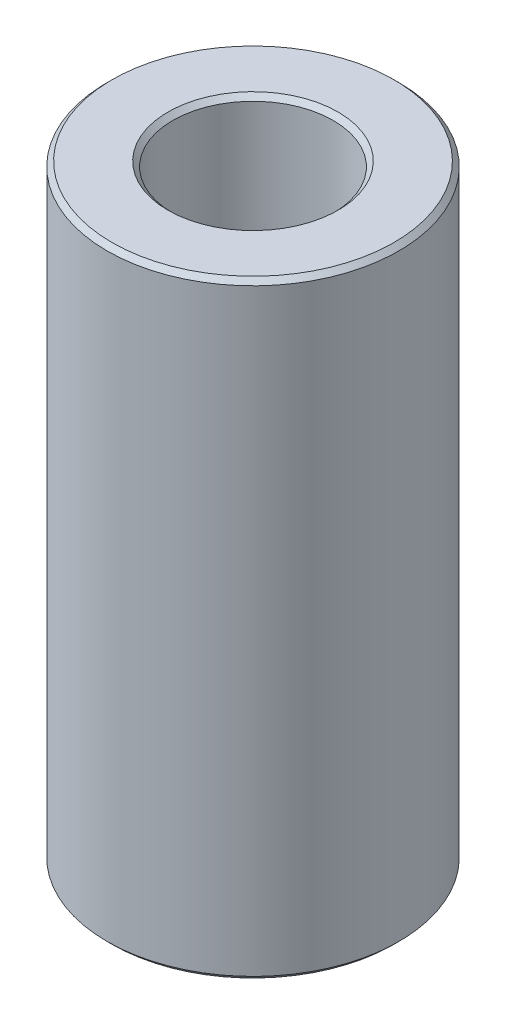
SolidWorks part; units mm, degrees
ref_plane "Front Plane" through (0, 0, 0) normal (0, 0, 1) x (1, 0, 0)
ref_plane "Top Plane" through (0, 0, 0) normal (0, 1, 0) x (1, 0, 0)
ref_plane "Right Plane" through (0, 0, 0) normal (1, 0, 0) x (0, 0, -1)
sketch "Sketch1" plane through (0, 0, 0) normal (0, 1, 0) x (1, 0, 0)
  circle A0 centre (0, 0) radius 6
  dimension "D1" = 12
extrude "Boss-Extrude1" add sketch "Sketch1" along normal blind 25
hole_wizard "M6 Clearance Hole1" positions "Sketch2" profile "Sketch3" hole size "M6" standard "ANSI Metric" end condition through all
sketch "Sketch2" plane through (0, 25, 0) normal (0, 1, 0) x (1, 0, 0)
  point P0 (0, 0)
sketch "Sketch3" plane through (0, 25, 0) normal (1, 0, 0) x (0, 0, 1)
  line L0 (0, 0) -> (0, 25)
  line L1 (0, 25) -> (3.3, 25)
  line L2 (3.3, 25) -> (3.3, 0)
  line L5 (3.3, 0) -> (0, 0)
  line L11 (0, -6.35) -> (0, 107.95) construction
  dimension "Thru Hole Dia." = 6.6
  dimension "Thru Hole Depth" = 25
chamfer "Chamfer1" distance 0.2 angle 45 4 edges at (0, 0, 6) (0, 25, 6) (0, 0, 3.3) (0, 25, 3.3)
